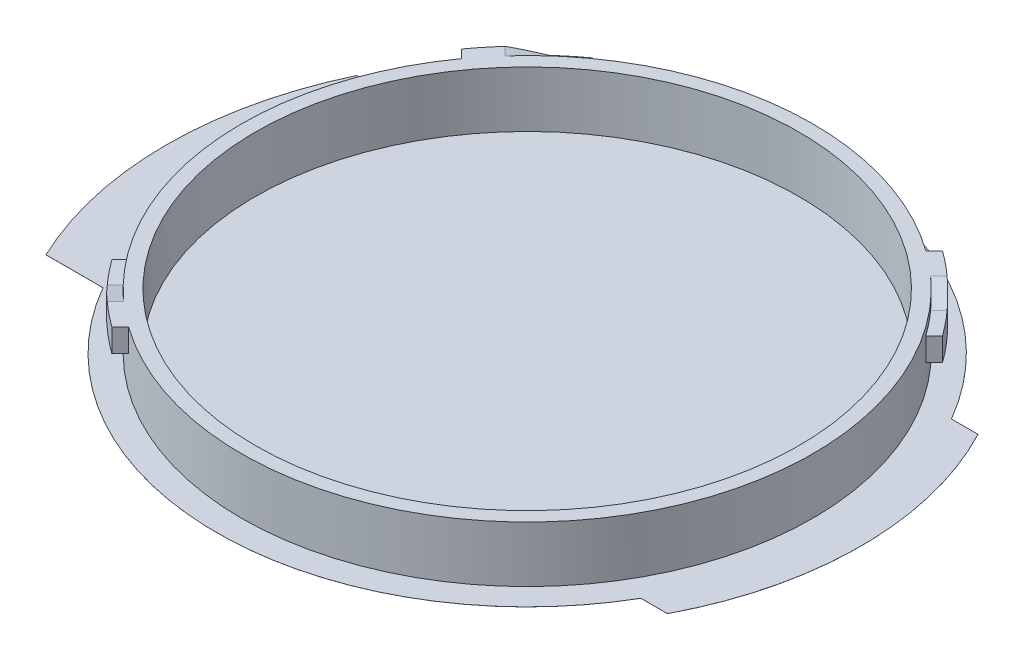
SolidWorks part; units mm, degrees
ref_plane "Płaszczyzna przednia" through (0, 0, 0) normal (0, 0, 1) x (1, 0, 0)
ref_plane "Płaszczyzna górna" through (0, 0, 0) normal (0, 1, 0) x (1, 0, 0)
ref_plane "Płaszczyzna prawa" through (0, 0, 0) normal (1, 0, 0) x (0, 0, -1)
sketch "Sketch1" plane through (0, 0, 0) normal (0, 1, 0) x (1, 0, 0)
  line L0 (-20.9896, 10) -> (-17.3205, 10)
  line L1 (-20.9896, -10) -> (-17.3205, -10)
  line L2 (17.3205, 10) -> (19.0329, 10)
  line L3 (17.3205, -10) -> (19.0329, -10)
  line L4 (0, 0) -> (-23.25, 0) construction
  arc A0 (17.3205, 10) -> (-17.3205, 10) centre (0, 0) ccw
  arc A1 (-20.9896, 10) -> (-20.9896, -10) centre (0, 0) ccw
  arc A3 (19.0329, -10) -> (19.0329, 10) centre (0, 0) ccw
  arc A4 (-17.3205, -10) -> (17.3205, -10) centre (0, 0) ccw
  dimension "D1" = 40
  dimension "D2" = 46.5
  dimension "D3" = 21.5
  dimension "D4" = 20
extrude "Boss-Extrude1" add sketch "Sketch1" along normal blind 1
sketch "Sketch2" plane through (0, 1, 0) normal (0, 1, 0) x (1, 0, 0)
  circle A0 centre (0, 0) radius 18.4
  circle A1 centre (0, 0) radius 17.5
  dimension "D1" = 36.8
  dimension "D2" = 35
extrude "Boss-Extrude2" add sketch "Sketch2" along normal blind 3.6
chamfer "Chamfer1" distance 4 angle 14 8 edges at (-19.155, 0, -10) (-23.25, 0, 0) (-19.155, 0, 10) (0, 0, 20) (18.1767, 0, 10) (21.5, 0, 0) (18.1767, 0, -10) (0, 0, -20) first distance on face at (-0.4633, 0, 0)
sketch "Sketch6" plane through (0, 1, 0) normal (0, 1, 0) x (1, 0, 0)
  line L0 (0, 0) -> (-10.6226, -10.6226) construction
  line L1 (0, 0) -> (-23.25, 0) construction
  dimension "D1" = 45
ref_plane "Plane3" through (-10.6226, 1, 10.6226) normal (-0.7071, 0, 0.7071) x (0.7071, 0, 0.7071)
sketch "Sketch3" plane through (0, 0, 0) normal (0, -1, 0) x (1, 0, 0)
  line L1 (-0.6, 5) -> (0.6, 5)
  line L2 (-0.6, 5) -> (-0.6, -5)
  line L3 (-0.6, -5) -> (0.6, -5)
  line L4 (0.6, 5) -> (0.6, -5)
  line L5 (-0.6, 5) -> (0.6, -5) construction
  line L6 (-0.6, -5) -> (0.6, 5) construction
  point P0 (0, 0)
  dimension "D1" = 1.2
  dimension "D2" = 10
extrude "Cut-Extrude1" cut sketch "Sketch3" against normal blind 0.5
ref_plane "Plane1" through (17.6616, 1, -17.6616) normal (-0.7071, 0, 0.7071) x (0.7071, 0, 0.7071)
sketch "Sketch4" plane through (17.6616, 1, -17.6616) normal (-0.7071, 0, 0.7071) x (0.7071, 0, 0.7071)
  line L0 (-3, 3.6) -> (-1, 3.6)
  line L1 (-1, 3.6) -> (1, 3.1)
  line L2 (1, 3.1) -> (3, 3.1)
  line L3 (3, 3.1) -> (3, 1.6)
  line L4 (3, 1.6) -> (1, 1.6)
  line L5 (1, 1.6) -> (-1, 2.1)
  line L6 (-1, 2.1) -> (-3, 2.1)
  line L7 (-3, 2.1) -> (-3, 3.6)
  line L8 (0, 3.35) -> (0, -1) construction
  line L9 (18.4, 3.6) -> (-18.4, 3.6) construction
  dimension "D1" = 6
  dimension "D2" = 2
  dimension "D3" = 2
  dimension "D4" = 2
  dimension "D5" = 2
  dimension "D6" = 2
  dimension "D7" = 1.5
extrude "Boss-Extrude3" add sketch "Sketch4" along normal up to next
pattern_circular "CirPattern1" count 3 every 90 about axis through (0, 4.6, 0) along (0, -1, 0) of "Boss-Extrude3" reverse direction yes
ref_plane "Plane2" through (0, 5, 0) normal (0, 1, 0) x (1, 0, 0)
sketch "Sketch5" plane through (0, 5, 0) normal (0, 1, 0) x (1, 0, 0)
  circle A0 centre (0, 0) radius 19.15
  circle A1 centre (0, 0) radius 34.2844
  dimension "D1" = 38.3
extrude "Cut-Extrude2" cut sketch "Sketch5" against normal blind 4
